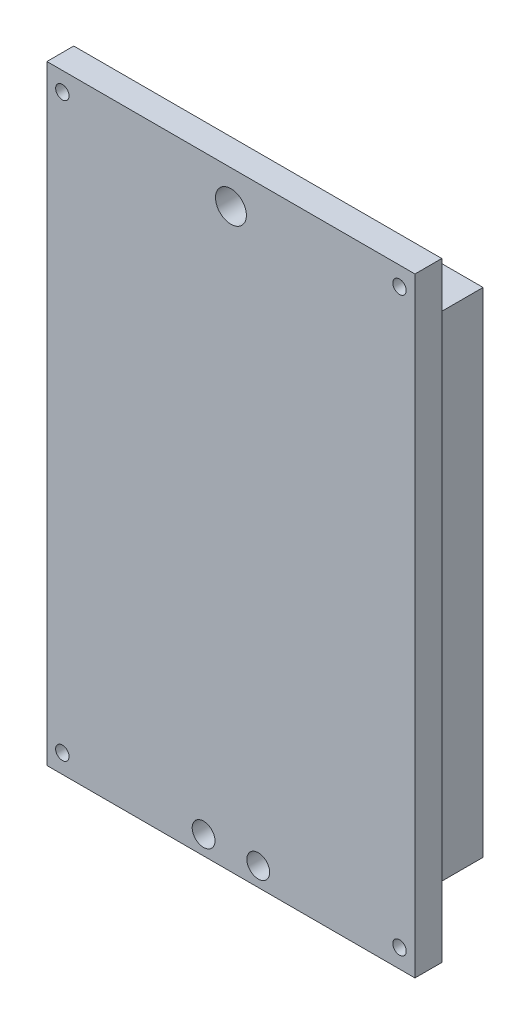
SolidWorks part; units mm, degrees
ref_plane "Front" through (0, 0, 0) normal (0, 0, 1) x (1, 0, 0)
ref_plane "Top" through (0, 0, 0) normal (0, 1, 0) x (1, 0, 0)
ref_plane "Right" through (0, 0, 0) normal (1, 0, 0) x (0, 0, -1)
sketch "arduinoOutline" plane through (0, 0, 0) normal (0, 0, 1) x (1, 0, 0)
  line L0 (0, 32.73) -> (2.54, 35.27) construction
  line L2 (0, 0) -> (0, 32.73) construction
  line L5 (2.54, 35.27) -> (2.54, 36.81) construction
  line L6 (3.54, 37.81) -> (67.6, 37.81) construction
  line L7 (68.6, 36.81) -> (68.6, -14.59) construction
  line L8 (67.6, -15.59) -> (4.06, -15.59) construction
  line L9 (4.06, -15.59) -> (2.54, -14.07) construction
  line L10 (2.54, -14.07) -> (2.54, -2.54) construction
  line L11 (2.54, -2.54) -> (0, 0) construction
  arc A0 (2.54, 36.81) -> (3.54, 37.81) centre (3.54, 36.81) cw construction
  arc A1 (68.6, -14.59) -> (67.6, -15.59) centre (67.6, -14.59) cw construction
  arc A2 (67.6, 37.81) -> (68.6, 36.81) centre (67.6, 36.81) cw construction
  point P8 (2.54, 37.81)
  point P13 (68.6, -15.59)
  point P16 (68.6, 37.81)
  dimension "D6" = 1
  dimension "D9" = 1
  dimension "D10" = 1
  dimension "D1" = 32.73
  dimension "D2" = 135
  dimension "D3" = 3.5921
  dimension "D4" = 2.54
  dimension "D5" = 66.06
  dimension "D7" = 53.4
  dimension "D8" = 64.54
  dimension "D11" = 135
  dimension "D12" = 2.1496
  dimension "D13" = 11.53
  dimension "D14" = 135
  dimension "D15" = 3.5921
sketch "arduinoMountingHolesSketch" plane through (0, 0, 0) normal (0, 0, 1) x (1, 0, 0)
  line L0 (0, 0) -> (0, 32.73) construction
  line L1 (67.6, -15.59) -> (4.06, -15.59) construction
  line L2 (3.54, 37.81) -> (67.6, 37.81) construction
  line L3 (68.6, 36.81) -> (68.6, -14.59) construction
  circle A0 centre (2.54, 2.28) radius 1.25
  circle A1 centre (2.54, 30.45) radius 1.25
  circle A2 centre (54.6, 35.27) radius 1.25
  circle A3 centre (53.35, -13.05) radius 1.25
  dimension "D9" = 2.5
  dimension "D1" = 2.54
  dimension "D2" = 17.87
  dimension "D3" = 2.54
  dimension "D4" = 7.36
  dimension "D5" = 2.54
  dimension "D6" = 14
  dimension "D7" = 2.54
  dimension "D8" = 15.25
sketch "9VbatteryMountingHolesSketch" plane through (0, 0, 0) normal (0, 0, 1) x (1, 0, 0)
  line L0 (0, 16.365) -> (68.6, 16.365) construction
  line L1 (4.875, 40.31) -> (63.725, 40.31) construction
  line L2 (4.875, 40.31) -> (4.875, 88.56) construction
  line L3 (4.875, 88.56) -> (63.725, 88.56) construction
  line L4 (63.725, 40.31) -> (63.725, 88.56) construction
  line L5 (0, 0) -> (0, 32.73) construction
  line L6 (68.6, 36.81) -> (68.6, -14.59) construction
  line L7 (34.3, 40.31) -> (34.3, 88.56) construction
  line L8 (4.875, 64.435) -> (63.725, 64.435) construction
  line L10 (3.54, 37.81) -> (67.6, 37.81) construction
  circle A0 centre (8.625, 86.06) radius 1.25
  circle A1 centre (59.975, 86.06) radius 1.25
  circle A2 centre (8.625, 42.81) radius 1.25
  circle A3 centre (59.975, 42.81) radius 1.25
  point P4 (34.3, 16.365)
  point P5 (34.3, 88.56)
  dimension "D3" = 2.5
  dimension "D1" = 48.25
  dimension "D2" = 58.85
  dimension "D4" = 2.5
  dimension "D5" = 3.75
  dimension "D6" = 2.5
sketch "legBracketMountingHolesSketch" plane through (0, 0, 0) normal (0, 0, 1) x (1, 0, 0)
  line L0 (34.3, 91.06) -> (34.3, 98.06) construction
  line L1 (24.1051, 98.06) -> (44.4949, 98.06) construction
  line L2 (24.1051, 98.06) -> (24.1051, 91.06) construction
  line L3 (24.1051, 91.06) -> (44.4949, 91.06) construction
  line L4 (44.4949, 98.06) -> (44.4949, 91.06) construction
  circle A0 centre (29.2026, 94.56) radius 2
  circle A1 centre (39.3974, 94.56) radius 2
  point P4 (24.1051, 94.56)
  point P5 (34.3, 98.06)
  dimension "D4" = 4
  dimension "D1" = 7
  dimension "D2" = 20.3898
  dimension "D3" = 2.5
  dimension "D5" = 5.0974
sketch "backsideMountingHolesSketch" plane through (0, 0, 0) normal (0, 0, 1) x (1, 0, 0)
  line L0 (0, 41.235) -> (68.6, 41.235) construction
  line L9 (0, 0) -> (0, 32.73) construction
  line L10 (34.3, 40.31) -> (34.3, 88.56) construction
  line L11 (68.6, 36.81) -> (68.6, -14.59) construction
  line L12 (24.1051, 98.06) -> (44.4949, 98.06) construction
  line L13 (4.875, 88.56) -> (63.725, 88.56) construction
  line L14 (4.875, 40.31) -> (4.875, 88.56) construction
  circle A1 centre (2.875, 94.56) radius 1.25
  circle A5 centre (65.725, 94.56) radius 1.25
  circle A6 centre (65.725, -12.09) radius 1.25
  circle A7 centre (2.875, -12.09) radius 1.25
  dimension "D1" = 2.5
  dimension "D2" = 56.825
  dimension "D3" = 6
  dimension "D4" = 2
sketch "Sketch1" plane through (0, 0, 0) normal (0, 0, 1) x (1, 0, 0)
  line L0 (67.6, -15.59) -> (4.06, -15.59) construction
  line L1 (0, 98.06) -> (68.6, 98.06)
  line L2 (0, 98.06) -> (0, -15.59)
  line L3 (0, -15.59) -> (68.6, -15.59)
  line L4 (68.6, 98.06) -> (68.6, -15.59)
  line L5 (0, 0) -> (0, 32.73) construction
  line L6 (68.6, 36.81) -> (68.6, -14.59) construction
  line L9 (24.1051, 98.06) -> (44.4949, 98.06) construction
extrude "bracketBase" add sketch "Sketch1" along normal blind 5
extrude "arduinoMountingHoles" cut sketch "arduinoMountingHolesSketch" against normal through all and the other way blind 22
extrude "9VbatteryMountingHoles" cut sketch "9VbatteryMountingHolesSketch" along normal blind 20
extrude "legBracketMountingHoles" cut sketch "legBracketMountingHolesSketch" along normal blind 13
extrude "backsideMountingHoles" cut sketch "backsideMountingHolesSketch" along normal blind 24
sketch "Sketch2" plane through (0, 0, 5) normal (0, 0, 1) x (1, 0, 0)
  circle A0 centre (53.35, -13.05) radius 1.25 construction
  circle A1 centre (2.54, 2.28) radius 1.25 construction
  circle A2 centre (2.54, 30.45) radius 1.25 construction
  circle A3 centre (54.6, 35.27) radius 1.25 construction
  circle A4 centre (59.975, 42.81) radius 1.25 construction
  circle A5 centre (8.625, 42.81) radius 1.25 construction
  circle A6 centre (59.975, 86.06) radius 1.25 construction
  circle A7 centre (39.3974, 94.56) radius 2 construction
  circle A8 centre (29.2026, 94.56) radius 2 construction
  circle A9 centre (8.625, 86.06) radius 1.25 construction
  circle A10 centre (53.35, -13.05) radius 1.25
  circle A11 centre (2.54, 2.28) radius 1.25
  circle A12 centre (2.54, 30.45) radius 1.25
  circle A13 centre (54.6, 35.27) radius 1.25
  circle A14 centre (59.975, 42.81) radius 1.25
  circle A15 centre (8.625, 42.81) radius 1.25
  circle A16 centre (59.975, 86.06) radius 1.25
  circle A17 centre (39.3974, 94.56) radius 2
  circle A18 centre (29.2026, 94.56) radius 2
  circle A19 centre (8.625, 86.06) radius 1.25
extrude "cover" add sketch "Sketch2" against normal up to surface (5 mm away) up to face at (1.625, -12.09, 0)
sketch "Sketch3" plane through (0, 0, 5) normal (0, 0, 1) x (1, 0, 0)
  line L1 (68.6, 98.06) -> (0, 98.06) construction
  line L2 (0, 98.06) -> (0, -15.59) construction
  line L3 (2.3, -4.765) -> (2.3, 87.235)
  line L4 (5.3, -1.765) -> (63.3, -1.765)
  line L5 (5.3, -1.765) -> (5.3, 84.235)
  line L6 (5.3, 84.235) -> (63.3, 84.235)
  line L7 (63.3, -1.765) -> (63.3, 84.235)
  line L8 (5.3, -1.765) -> (63.3, 84.235) construction
  line L9 (5.3, 84.235) -> (63.3, -1.765) construction
  line L10 (2.3, 87.235) -> (66.3, 87.235)
  line L11 (66.3, -4.765) -> (66.3, 87.235)
  line L12 (2.3, -4.765) -> (66.3, -4.765)
  point P4 (34.3, 98.06)
  point P5 (0, 41.235)
  point P6 (34.3, 41.235)
  dimension "D1" = 86
  dimension "D2" = 58
  dimension "D3" = 3
extrude "breadBoardCavity" add sketch "Sketch3" along normal blind 10
ref_plane "Plane1" through (0, 0, 2.5) normal (0, 0, 1) x (1, 0, 0)
mirror "Mirror1" about plane through (0, 0, 2.5) normal (0, 0, 1) of "breadBoardCavity"
sketch "Sketch4" plane through (0, 87.235, 0) normal (0, 1, 0) x (1, 0, 0)
  line L4 (66.3, -5) -> (2.3, -5)
  line L5 (2.3, -5) -> (2.3, -15)
  line L6 (2.3, -15) -> (66.3, -15)
  line L7 (66.3, -15) -> (66.3, -5)
  line L8 (66.3, -5) -> (2.3, -5)
  line L9 (2.3, -5) -> (2.3, -15)
  line L10 (2.3, -15) -> (66.3, -15)
  line L11 (66.3, -15) -> (66.3, -5)
  dimension "D1" = 0
extrude "Cut-Extrude1" cut sketch "Sketch4" against normal through all
sketch "Sketch5" plane through (0, 0, 0) normal (0, 0, -1) x (-1, 0, 0)
  line L0 (-66.3, 87.235) -> (-2.3, 87.235) construction
  line L1 (-68.6, 98.06) -> (0, 98.06) construction
  circle A0 centre (-34.3, 91.81) radius 2.875
  point P2 (-34.3, 98.06)
  point P9 (-34.3, 94.685)
  dimension "D1" = 5.75
  dimension "D2" = 4.575
extrude "toggleSwitchHole" cut sketch "Sketch5" against normal blind 10
sketch "Sketch6" plane through (0, 0, 0) normal (0, 0, -1) x (-1, 0, 0)
  line L0 (-34.3, -15.59) -> (-34.3, 98.06) construction
  line L1 (0, -15.59) -> (-68.6, -15.59) construction
  line L2 (-68.6, 98.06) -> (0, 98.06) construction
  circle A0 centre (-39.3974, -12.09) radius 2.125
  circle A1 centre (-29.2026, -12.09) radius 2.125
  dimension "D1" = 4.25
  dimension "D2" = 3.5
  dimension "D3" = 5.0974
extrude "Cut-Extrude2" cut sketch "Sketch6" against normal blind 10
equation "\"D2@backsideMountingHolesSketch\"=113.65mm/2"
